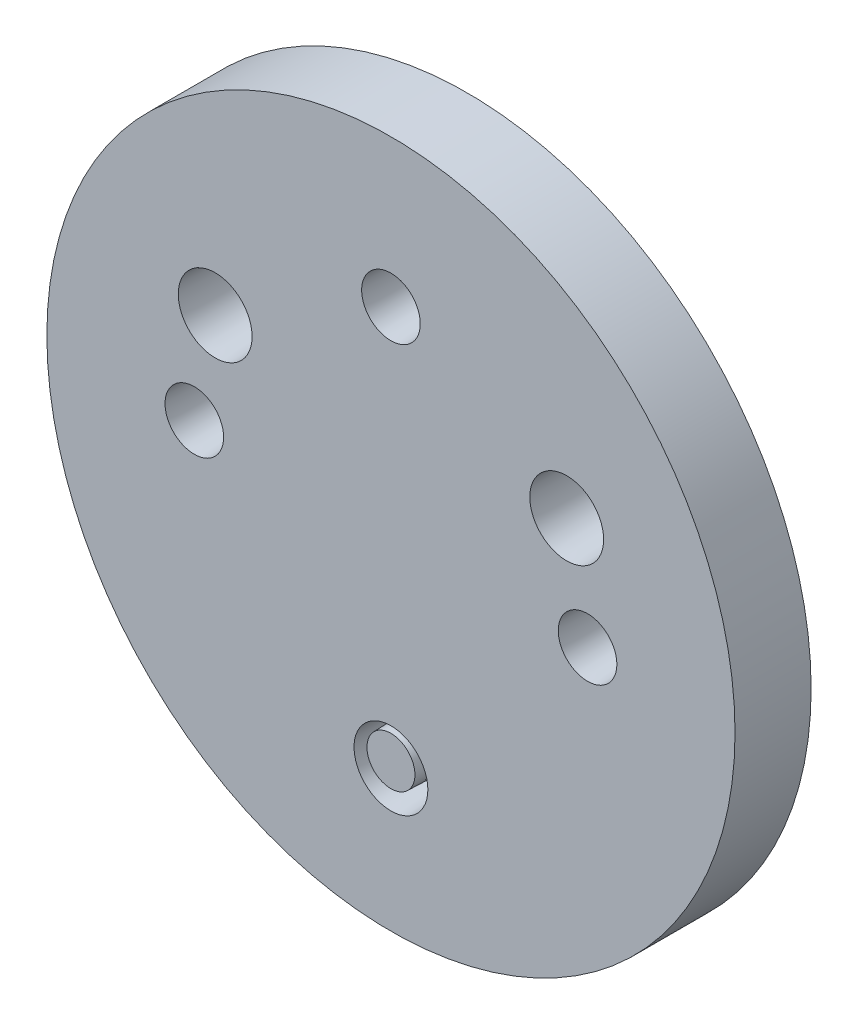
SolidWorks part; units mm, degrees
other "Markup1"
sketch "Sketch6" plane through (31.1257, -31.1257, 6.6) normal (0.5824, -0.4463, 0.6794) x (0.0162, 0.842, 0.5392)
ref_plane "Front Plane" through (0, 0, 0) normal (1, 0, 0) x (0, 1, 0)
ref_plane "Top Plane" through (0, 0, 0) normal (0, 0, 1) x (0, 1, 0)
ref_plane "Right Plane" through (0, 0, 0) normal (0, 1, 0) x (-1, 0, 0)
sketch "Sketch1" plane through (0, 0, 0) normal (0, 0, 1) x (0, 1, 0)
  circle A0 centre (0, 0) radius 27.125
  dimension "D1" = 54.25
extrude "Boss-Extrude1" add sketch "Sketch1" along normal blind 6 contours A0 region at (0, 0, 0)
sketch "Sketch2" plane through (0, 0, 6) normal (0, 0, -1) x (1, 0, 0)
  circle A0 centre (0, 0) radius 16 construction
  circle A1 centre (0, 16) radius 2.7
  circle A2 centre (13.8564, -8) radius 2.7
  circle A3 centre (-13.8564, -8) radius 2.7
  circle A4 centre (0, 0) radius 15.5 construction
  circle A5 centre (-15.5, 0) radius 2.1
  circle A11 centre (0, 15.5) radius 2.1
  circle A12 centre (15.5, 0) radius 2.1
  circle A13 centre (0, -15.5) radius 2.1
  dimension "D1" = 32
  dimension "D2" = 5.4
  dimension "D4" = 31
  dimension "D5" = 4.2
  dimension "D3" = 3
  dimension "D6" = 4
extrude "Cut-Extrude1" cut sketch "Sketch2" against normal through all draft 2 from surface draft outward yes starting at face at (27.125, 0, 0)
equation "\"D4@Sketch2\"=31"
equation "\"SunTeeth\"= 12"
equation "\"PlanetTeeth\" = 20"
equation "\"Module\" = 1"
equation "\"OrbitDiameter\"= \"SunTeeth\" * \"Module\" + \"PlanetTeeth\" * \"Module\""
equation "\"RingDiameter\"= ( \"SunTeeth\" + 2 * \"PlanetTeeth\" ) * \"Module\""
equation "\"BearingBore\" = 4"
equation "\"D1@Sketch2\"=\"OrbitDiameter\""
equation "\"D2@Sketch2\"=5.4"
equation "\"PressureAngle\" = 20deg"
equation "\"GearWidth\"=10"
equation "\"BearingDiameter\" = 13"
equation "\"ShaftDiameter\"= 6.5"
equation "\"D1@Sketch1\"=( \"SunTeeth\" + 2 * \"PlanetTeeth\" ) * \"Module\"+ 2.25*\"Module\""
